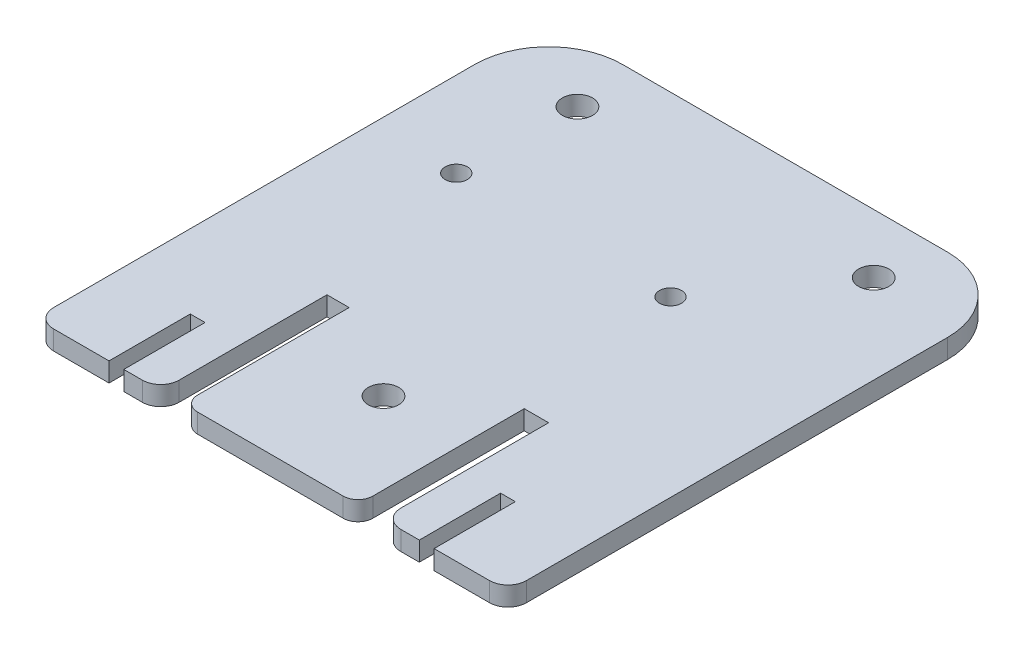
SolidWorks part; units mm, degrees
ref_plane "Front Plane" through (0, 0, 0) normal (0, 0, 1) x (1, 0, 0)
ref_plane "Top Plane" through (0, 0, 0) normal (0, 1, 0) x (1, 0, 0)
ref_plane "Right Plane" through (0, 0, 0) normal (1, 0, 0) x (0, 0, -1)
sketch "Sketch1" plane through (0, 0, 0) normal (0, 1, 0) x (1, 0, 0)
  line L0 (11.7, -23.5) -> (32, -23.5)
  line L1 (-32, -23.5) -> (-12, -23.5)
  line L2 (-32, -23.5) -> (-32, 13.5)
  line L3 (-22, 23.5) -> (22, 23.5)
  line L4 (32, -23.5) -> (32, 13.5)
  line L5 (-32, -23.5) -> (32, 23.5) construction
  line L6 (-32, 23.5) -> (32, -23.5) construction
  line L8 (-12, -23.5) -> (-12, -46)
  line L9 (-12, -46) -> (11.7, -46)
  line L10 (11.7, -23.5) -> (11.7, -46)
  arc A0 (-32, 13.5) -> (-22, 23.5) centre (-22, 13.5) cw
  arc A1 (32, 13.5) -> (22, 23.5) centre (22, 13.5) ccw
  point P0 (0, 0)
  dimension "D6" = 10
  dimension "D7" = 10
  dimension "D1" = 64
  dimension "D2" = 47
  dimension "D3" = 20
  dimension "D4" = 23.7
  dimension "D5" = 22.5
extrude "Main Body" add sketch "Sketch1" along normal blind 2.6
sketch "Sketch2" plane through (0, 2.6, 0) normal (0, 1, 0) x (1, 0, 0)
  line L0 (22, 23.5) -> (-22, 23.5) construction
  line L1 (-32, 13.5) -> (-32, -23.5) construction
  line L2 (0, 0) -> (0, 23.5) construction
  line L3 (32, -23.5) -> (32, 13.5) construction
  line L6 (-12, -23.5) -> (-12, -46) construction
  line L8 (-20.5, -0.5) -> (-22, -0.5) construction
  line L9 (8.5, -0.5) -> (10, -0.5) construction
  circle A0 centre (-20.1, 15.5) radius 2.05
  circle A1 centre (20, 15.5) radius 2.05
  circle A3 centre (-20.5, -0.5) radius 1.5
  circle A4 centre (8.5, -0.5) radius 1.5
  circle A6 centre (0.7, -31.55) radius 2.05
  dimension "D1" = 4.1
  dimension "D4" = 4.1
  dimension "D7" = 29
  dimension "D8" = 3
  dimension "D9" = 3
  dimension "D10" = 22
  dimension "D11" = 4.1
  dimension "D2" = 8
  dimension "D3" = 11.9
  dimension "D5" = 8
  dimension "D6" = 12
  dimension "D20" = 12.7
  dimension "D21" = 47.05
extrude "Screw holes" cut sketch "Sketch2" against normal through all both and the other way through all
fillet "Main lower body Fillet" radius 2 2 edges at (11.7, 1.3, 46) (-12, 1.3, 46)
sketch "Sketch4" plane through (0, 2.6, 0) normal (0, 1, 0) x (1, 0, 0)
  line L1 (-32, -23.5) -> (-15, -23.5)
  line L2 (-32, -23.5) -> (-32, -21)
  line L3 (-32, -21) -> (-15, -21)
  line L4 (-15, -23.5) -> (-15, -21)
  line L5 (32, -23.5) -> (15, -23.5)
  line L6 (32, -23.5) -> (32, -21)
  line L7 (32, -21) -> (15, -21)
  line L8 (15, -23.5) -> (15, -21)
  dimension "D1" = 2.5
  dimension "D2" = 2.5
  dimension "D3" = 17
  dimension "D4" = 17
sketch "Sketch5" plane through (0, 0, 23.5) normal (0, 0, 1) x (1, 0, 0)
  line L0 (-32, 0) -> (-12, 0) construction
  line L1 (-32, 2.6) -> (-15, 2.6)
  line L2 (-32, 2.6) -> (-32, 0)
  line L3 (-32, 0) -> (-15, 0)
  line L4 (-15, 2.6) -> (-15, 0)
  line L5 (11.7, 0) -> (32, 0) construction
  line L6 (32, 2.6) -> (15, 2.6)
  line L7 (32, 2.6) -> (32, 0)
  line L8 (32, 0) -> (15, 0)
  line L9 (15, 2.6) -> (15, 0)
  dimension "D1" = 17
  dimension "D2" = 17
extrude "Boss-Extrude1" add sketch "Sketch5" along normal blind 22.5
sketch "Sketch6" plane through (0, 2.6, 0) normal (0, 1, 0) x (1, 0, 0)
  line L0 (-15, -46) -> (-32, -46) construction
  line L1 (-20, -46) -> (-22, -46)
  line L2 (-20, -46) -> (-20, -35)
  line L3 (-20, -35) -> (-22, -35)
  line L4 (-22, -46) -> (-22, -35)
  line L5 (32, -46) -> (15, -46) construction
  line L6 (22, -46) -> (20, -46)
  line L7 (22, -46) -> (22, -35)
  line L8 (22, -35) -> (20, -35)
  line L9 (20, -46) -> (20, -35)
  line L10 (-32, 13.5) -> (-32, -46) construction
  line L11 (32, -46) -> (32, 13.5) construction
  point P16 (21, -35)
  dimension "D1" = 12
  dimension "D2" = 12
  dimension "D3" = 10
  dimension "D4" = 10
  dimension "D5" = 11
  dimension "D6" = 11
extrude "Cut-Extrude1" cut sketch "Sketch6" against normal blind 22.5
fillet "Fillet2" radius 2.5 4 edges at (-32, 1.3, 46) (-15, 1.3, 46) (15, 1.3, 46) (32, 1.3, 46)
